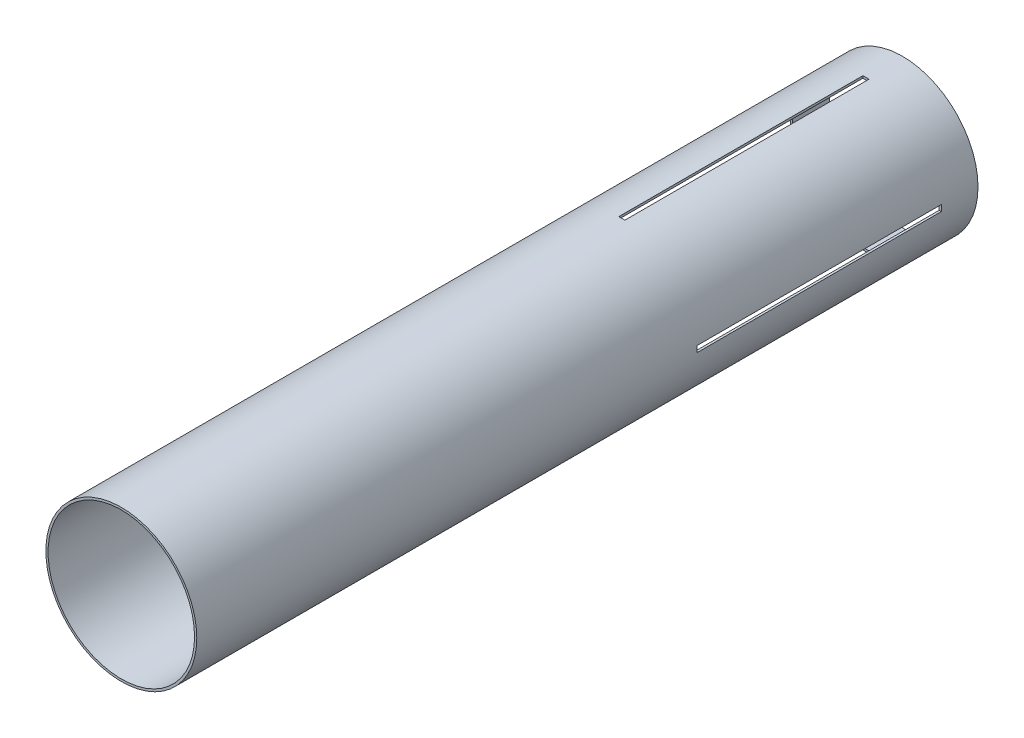
SolidWorks part; units mm, degrees
ref_plane "Front Plane" through (0, 0, 0) normal (0, 0, 1) x (1, 0, 0)
ref_plane "Top Plane" through (0, 0, 0) normal (0, 1, 0) x (1, 0, 0)
ref_plane "Right Plane" through (0, 0, 0) normal (1, 0, 0) x (0, 0, -1)
sketch "Sketch1" plane through (0, 0, 0) normal (0, 0, 1) x (1, 0, 0)
  circle A0 centre (0, 0) radius 39.2557
  circle A1 centre (0, 0) radius 38.1
  dimension "D2" = 78.5114
extrude "Boss-Extrude1" add sketch "Sketch1" along normal mid plane 406.4
sketch "Sketch3" plane through (0, 0, 0) normal (0, 1, 0) x (1, 0, 0)
  line L0 (39.2557, 203.2) -> (-39.2557, 203.2) construction
  line L1 (1.5875, 57.15) -> (-1.5875, 57.15)
  line L2 (1.5875, 57.15) -> (1.5875, 184.15)
  line L3 (1.5875, 184.15) -> (-1.5875, 184.15)
  line L4 (-1.5875, 57.15) -> (-1.5875, 184.15)
  line L5 (1.5875, 57.15) -> (-1.5875, 184.15) construction
  line L6 (1.5875, 184.15) -> (-1.5875, 57.15) construction
  line L7 (39.2557, 203.2) -> (-39.2557, 203.2) construction
  point P0 (0, 120.65)
  dimension "D1" = 3.175
  dimension "D2" = 127
  dimension "D3" = 19.05
extrude "Cut-Extrude1" cut sketch "Sketch3" along normal through all
pattern_circular "CirPattern1" count 4 over 360 about axis through (0, 0, 203.2) along (0, 0, -1) of "Cut-Extrude1" reverse direction yes
equation "\"AIRFRAME_OD\"= 3.091in"
equation "\"AIRFRAME_ID\"= 3.00in"
equation "\"FLAT_T\"= 0.125in"
equation "\"NOSE_EXP_L\"= 3.5in"
equation "\"NOSE_SHOULDER_L\"= 5in"
equation "\"MAIN_L\"= 30in"
equation "\"RECO_COUP_L\"= 6in"
equation "\"RECO_SWITCH_L\"= 1.5in"
equation "\"DROGUE_L\"= 14in"
equation "\"ATS_FORE_COUP_L\"= 4in"
equation "\"ATS_AFT_COUP_L\"= 2.5in"
equation "\"LOWER_L\"= 16in"
equation "\"FIN_N\"= 4"
equation "\"CR_AFT_X\"= 0.5in"
equation "\"CR_FORE_X\"= 6in"
equation "\"D1@Sketch1\"=\"AIRFRAME_ID\""
equation "\"D2@Sketch1\"=\"AIRFRAME_OD\""
equation "\"D1@Boss-Extrude1\"=\"LOWER_L\""
equation "\"FIN_ROOT\"= 5in"
equation "\"FIN_X\"= 0.75in"
equation "\"MOTOR_OD\"= 2.25in"
equation "\"MOTOR_ID\"= 2.126in"
equation "\"D1@Sketch3\"=\"FLAT_T\""
equation "\"D2@Sketch3\"=\"FIN_ROOT\""
equation "\"D3@Sketch3\"=\"FIN_X\""
equation "\"D1@CirPattern1\"=\"FIN_N\""
